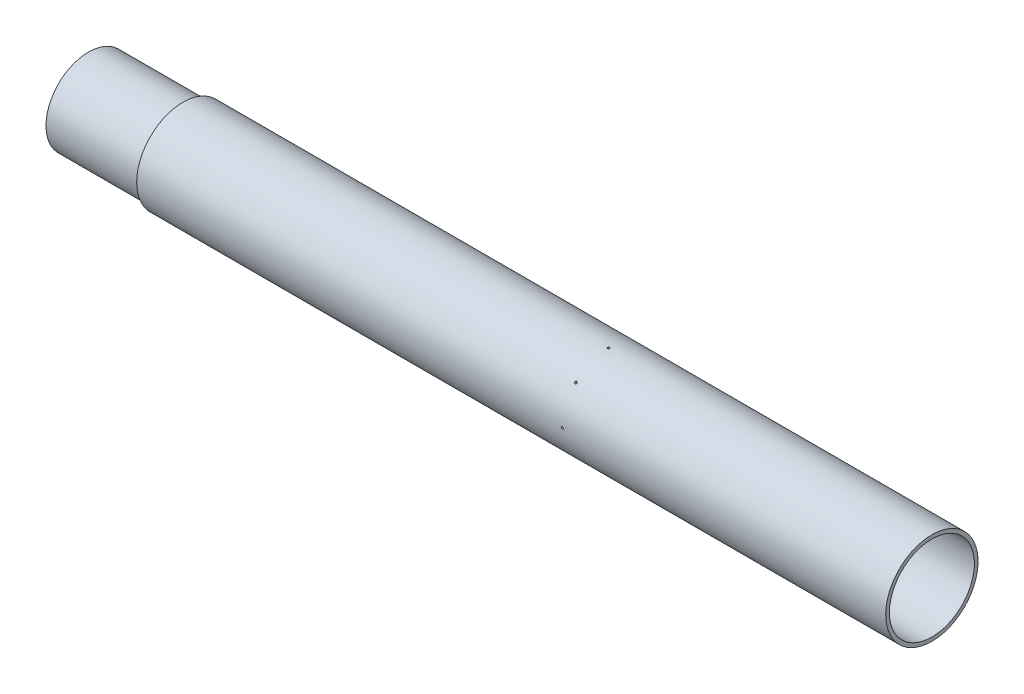
SolidWorks part; units mm, degrees
ref_plane "Front Plane" through (0, 0, 0) normal (0, 0, 1) x (1, 0, 0)
ref_plane "Top Plane" through (0, 0, 0) normal (0, 1, 0) x (1, 0, 0)
ref_plane "Right Plane" through (0, 0, 0) normal (1, 0, 0) x (0, 0, -1)
sketch "Sketch1" plane through (0, 0, 0) normal (0, 0, 1) x (1, 0, 0)
  line L0 (-1238.9107, 62.15) -> (-2246.5566, 62.15)
  line L1 (-2246.5566, 62.15) -> (-2246.5566, 57.15)
  line L2 (-2246.5566, 57.15) -> (-2373.5566, 57.15)
  line L3 (-2373.5566, 57.15) -> (-2373.5566, 52.15)
  line L4 (-2373.5566, 52.15) -> (-2119.5566, 52.15)
  line L5 (-2119.5566, 52.15) -> (-2119.5566, 57.15)
  line L6 (-2119.5566, 57.15) -> (-1238.9107, 57.15)
  line L7 (-1238.9107, 57.15) -> (-1238.9107, 62.15)
  line L8 (-2246.5566, 0) -> (-1840.7203, 0) construction
  dimension "D1" = 1007.6459
  dimension "D2" = 127
  dimension "D3" = 5
  dimension "D4" = 5
  dimension "D5" = 254
  dimension "D6" = 5
  dimension "D7" = 57.15
revolve "Revolve1" add sketch "Sketch1" angle 360 about L8
ref_plane "Plane1" through (0, 0, -62.15) normal (0, 0, -1) x (-1, 0, 0)
sketch "Sketch2" plane through (0, 0, -62.15) normal (0, 0, -1) x (-1, 0, 0)
  line L0 (1238.9107, 62.15) -> (1238.9107, -62.15) construction
  circle A0 centre (1673.9107, 0) radius 1.4224
  dimension "D2" = 2.8448
  dimension "D1" = 435
extrude "Cut-Extrude1" cut sketch "Sketch2" against normal blind 20
pattern_circular "CirPattern1" count 8 over 360 about axis through (-1238.9107, 0, 0) along (-1, 0, 0) of "Cut-Extrude1"
